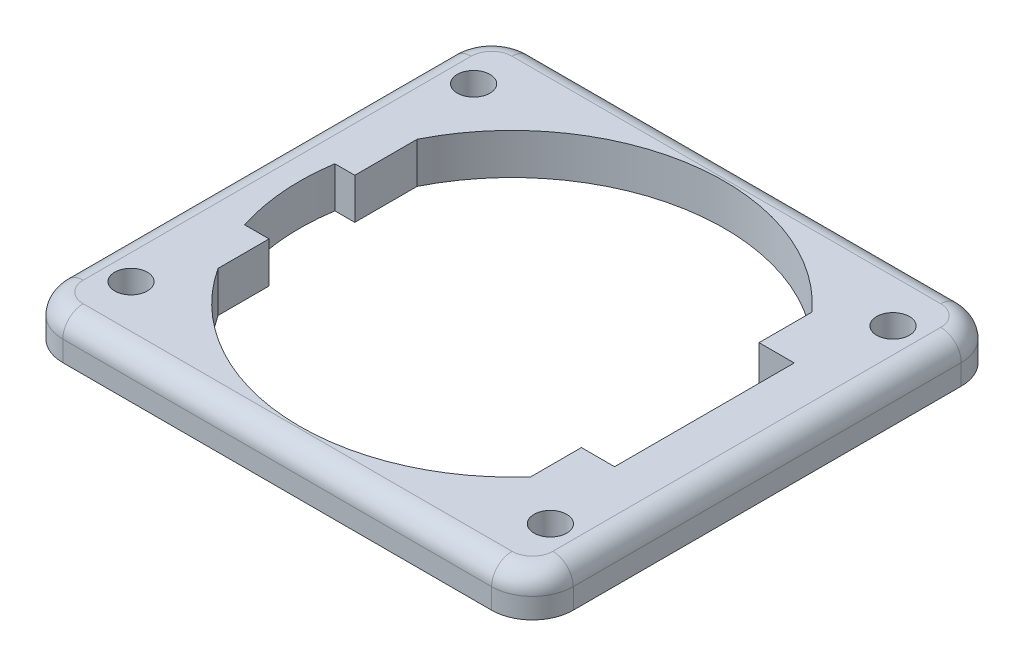
SolidWorks part; units mm, degrees
ref_plane "Front Plane" through (0, 0, 0) normal (0, 0, 1) x (1, 0, 0)
ref_plane "Top Plane" through (0, 0, 0) normal (0, 1, 0) x (1, 0, 0)
ref_plane "Right Plane" through (0, 0, 0) normal (1, 0, 0) x (0, 0, -1)
sketch "Sketch1" plane through (0, 0, 0) normal (0, 1, 0) x (1, 0, 0)
  line L0 (0, 0) -> (-68.453, 0) construction
  line L1 (-15.875, 14.605) -> (15.875, 14.605)
  line L2 (-15.875, 14.605) -> (-15.875, -14.605)
  line L3 (-15.875, -14.605) -> (15.875, -14.605)
  line L4 (15.875, 14.605) -> (15.875, -14.605)
  line L5 (0, 0) -> (0, 51.4629) construction
  point P9 (0, 14.605)
  point P12 (15.875, 0)
  dimension "D1" = 31.75
  dimension "D2" = 29.21
  dimension "D3" = 0
  dimension "D4" = 0
extrude "Boss-Extrude1" add sketch "Sketch1" along normal blind 2.54
sketch "Sketch2" plane through (0, 2.54, 0) normal (0, 1, 0) x (1, 0, 0)
  line L0 (0, 0) -> (0, 15.7929) construction
  line L1 (0, 0) -> (11.8972, 0) construction
  line L2 (11.9677, 5.588) -> (11.9677, -5.588)
  arc A0 (11.9677, 5.588) -> (11.9677, -5.588) centre (0, 0) ccw
  dimension "D1" = 13.208
  dimension "D2" = 11.176
  dimension "D3" = 0
  dimension "D4" = 0
extrude "Cut-Extrude1" cut sketch "Sketch2" against normal through all
sketch "Sketch3" plane through (0, 2.54, 0) normal (0, 1, 0) x (1, 0, 0)
  line L0 (0, 0) -> (0, 8.1201) construction
  line L1 (-15.875, 6.296) -> (-11.811, 6.296)
  line L2 (-15.875, 6.296) -> (-15.875, 2.032)
  line L3 (-15.875, 2.032) -> (-11.811, 2.032)
  line L4 (-11.811, 6.296) -> (-11.811, 2.032)
  line L5 (-15.875, -14.605) -> (-11.049, -14.605)
  line L6 (-15.875, -14.605) -> (-15.875, -4.064)
  line L7 (-15.875, -4.064) -> (-11.049, -4.064)
  line L8 (-11.049, -14.605) -> (-11.049, -4.064)
  line L9 (15.875, -5.588) -> (9.906, -5.588)
  line L10 (15.875, -5.588) -> (15.875, -10.0525)
  line L11 (15.875, -10.0525) -> (9.906, -10.0525)
  line L12 (9.906, -5.588) -> (9.906, -10.0525)
  line L13 (15.875, 10.2275) -> (9.779, 10.2275)
  line L14 (15.875, 10.2275) -> (15.875, 5.588)
  line L15 (15.875, 5.588) -> (9.779, 5.588)
  line L16 (9.779, 10.2275) -> (9.779, 5.588)
  line L17 (0, 0) -> (-6.4257, 0) construction
  line L18 (-15.875, 14.605) -> (-15.875, -14.605) construction
  line L19 (15.875, -14.605) -> (15.875, 14.605) construction
  line L20 (-15.875, -14.605) -> (15.875, -14.605) construction
  arc A0 (11.9677, 5.588) -> (11.9677, -5.588) centre (0, 0) ccw construction
  dimension "D1" = 0
  dimension "D2" = 2.032
  dimension "D3" = 11.811
  dimension "D4" = 5.588
  dimension "D5" = 5.588
  dimension "D6" = 9.779
  dimension "D7" = 9.906
  dimension "D8" = 0
  dimension "D9" = 0
  dimension "D10" = 11.049
  dimension "D11" = 0
  dimension "D12" = 0
  dimension "D13" = 10.541
extrude "Boss-Extrude2" add sketch "Sketch3" against normal blind 2.54
fillet "Fillet1" radius 1.27 4 edges at (0, 2.54, 14.605) (15.875, 2.54, 0) (0, 2.54, -14.605) (-15.875, 2.54, 0)
sketch "Sketch5" plane through (0, 0, 0) normal (0, -1, 0) x (1, 0, 0)
  line L0 (0, 0) -> (0, -21.2247) construction
  line L1 (0, 0) -> (32.0641, 0) construction
  circle A0 centre (13.0429, -10.6553) radius 1.016
  circle A1 centre (-13.0429, -10.6553) radius 1.016
  circle A2 centre (-13.0429, 10.6553) radius 1.016
  circle A3 centre (13.0429, 10.6553) radius 1.016
  dimension "D1" = 2.032
  dimension "D2" = 10.6553
  dimension "D3" = 13.0429
extrude "Cut-Extrude3" cut sketch "Sketch5" against normal through all
fillet "Fillet2" radius 2.54 8 edges at (15.503, 2.168, 14.233) (-15.503, 2.168, 14.233) (-15.503, 2.168, -14.233) (15.503, 2.168, -14.233) (15.875, 0.635, -14.605) (-15.875, 0.635, -14.605) (-15.875, 0.635, 14.605) (15.875, 0.635, 14.605)
